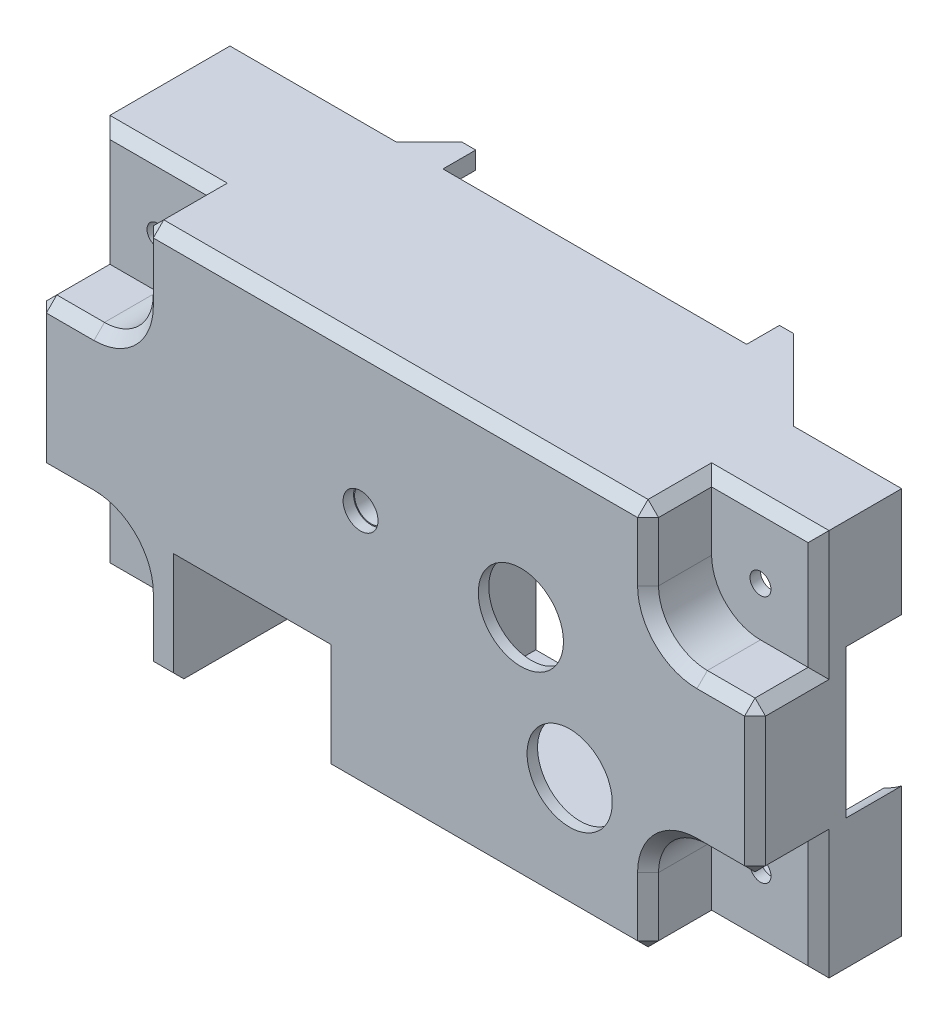
SolidWorks part; units mm, degrees
note: The reader was unsure of these and kept them because the rebuilt part matched: shared geometry of "Sketch6<3>".
ref_plane "Front Plane" through (0, 0, 0) normal (0, 0, 1) x (1, 0, 0)
ref_plane "Top Plane" through (0, 0, 0) normal (0, 1, 0) x (1, 0, 0)
ref_plane "Right Plane" through (0, 0, 0) normal (1, 0, 0) x (0, 0, -1)
sketch "Sketch1" plane through (0, 0, 0) normal (0, 0, 1) x (1, 0, 0)
  line L0 (36, -27.75) -> (29.2, -27.75) construction
  line L1 (36, -27.75) -> (51.5, -27.75) construction
  line L2 (51.5, -27.75) -> (51.5, 27.75) construction
  line L3 (51.5, 27.75) -> (36, 27.75) construction
  line L4 (-27.7, 27.75) -> (-51.5, 27.75) construction
  line L5 (-51.5, 27.75) -> (-51.5, 9.7141) construction
  line L6 (-51.5, 9.7141) -> (-51.5, 6.25) construction
  line L7 (-51.5, 6.25) -> (-51.5, -1.55) construction
  line L8 (-51.5, -1.55) -> (-51.5, -5.0141) construction
  line L9 (-51.5, -5.0141) -> (-51.5, -27.75) construction
  line L10 (-51.5, -27.75) -> (29.2, -27.75) construction
  line L11 (36, -27.75) -> (29.2, -27.75)
  line L12 (36, -27.75) -> (51.5, -27.75)
  line L13 (51.5, -27.75) -> (51.5, 27.75)
  line L14 (51.5, 27.75) -> (36, 27.75)
  line L15 (36, 27.75) -> (-51.5, 27.75)
  line L16 (-51.5, 27.75) -> (-51.5, 9.7141)
  line L17 (-51.5, 9.7141) -> (-51.5, 6.25)
  line L18 (-51.5, 6.25) -> (-51.5, -1.55)
  line L19 (-51.5, -1.55) -> (-51.5, -5.0141)
  line L20 (-51.5, -5.0141) -> (-51.5, -27.75)
  line L21 (-51.5, -27.75) -> (29.2, -27.75)
  line L22 (49, 25.25) -> (49, -25.25) construction
  line L23 (36, 25.25) -> (49, 25.25) construction
  line L24 (24.5, 25.25) -> (36, 25.25) construction
  line L25 (-23, 25.25) -> (24.5, 25.25) construction
  line L26 (-49, 25.25) -> (-27.7, 25.25) construction
  line L27 (49, -25.25) -> (36, -25.25) construction
  line L28 (36, -25.25) -> (29.2, -25.25) construction
  line L29 (29.2, -25.25) -> (-49, -25.25) construction
  line L30 (-49, -25.25) -> (-49, -5.0141) construction
  line L31 (-49, -5.0141) -> (-49, -1.55) construction
  line L32 (-49, -1.55) -> (-49, 6.25) construction
  line L33 (-49, 6.25) -> (-49, 9.7141) construction
  line L34 (-49, 9.7141) -> (-49, 25.25) construction
  line L35 (-27.7, 25.25) -> (-23, 25.25) construction
  line L36 (49, -25.25) -> (36, -25.25)
  line L37 (36, -25.25) -> (29.2, -25.25)
  line L38 (29.2, -25.25) -> (-49, -25.25)
  line L39 (-49, -25.25) -> (-49, -5.0141)
  line L40 (-49, -5.0141) -> (-49, -1.55)
  line L41 (-49, -1.55) -> (-49, 6.25)
  line L42 (-49, 6.25) -> (-49, 9.7141)
  line L43 (-49, 9.7141) -> (-49, 25.25)
  line L44 (49, 25.25) -> (49, -25.25)
  line L45 (36, 25.25) -> (49, 25.25)
  line L46 (24.5, 25.25) -> (36, 25.25)
  line L47 (-23, 25.25) -> (24.5, 25.25)
  line L48 (-27.7, 25.25) -> (-23, 25.25)
  line L49 (-49, 25.25) -> (-27.7, 25.25)
  line L50 (43.18, -9.28) -> (57.4441, -9.28)
  line L51 (34.68, -17.78) -> (34.68, -32.8438)
  line L52 (51.5, 0) -> (-51.5, 0) construction
  line L53 (0, 0) -> (0, -33.7504) construction
  line L54 (43.18, 9.28) -> (57.4441, 9.28)
  line L55 (34.68, 17.78) -> (34.68, 32.8438)
  line L56 (-34.68, -17.78) -> (-34.68, -32.8438)
  line L57 (-43.18, -9.28) -> (-57.4441, -9.28)
  line L58 (-34.68, 17.78) -> (-34.68, 32.8438)
  line L59 (-43.18, 9.28) -> (-57.4441, 9.28)
  line L64 (-10, -21.75) -> (-10, -12.25)
  line L65 (-10, -12.25) -> (-31, -12.25)
  line L66 (-31, -12.25) -> (-31, -21.75)
  line L67 (-31, -21.75) -> (-10, -21.75)
  line L68 (-10, -21.75) -> (-10, -12.25)
  line L69 (-10, -12.25) -> (-31, -12.25)
  line L70 (-31, -12.25) -> (-31, -21.75)
  line L71 (-31, -21.75) -> (-10, -21.75)
  line L72 (-5.5, 16.75) -> (-5.5, 23.25)
  line L73 (-5.5, 23.25) -> (-22, 23.25)
  line L74 (-22, 23.25) -> (-22, 16.75)
  line L75 (-22, 16.75) -> (-5.5, 16.75)
  line L76 (-5.5, 16.75) -> (-5.5, 23.25) construction
  line L77 (-5.5, 23.25) -> (-22, 23.25) construction
  line L78 (-22, 23.25) -> (-22, 16.75) construction
  line L79 (-22, 16.75) -> (-5.5, 16.75) construction
  line L80 (25, 16.75) -> (25, 23.25)
  line L81 (25, 23.25) -> (-1.8, 23.25)
  line L82 (-1.8, 23.25) -> (-1.8, 16.75)
  line L83 (-1.8, 16.75) -> (25, 16.75)
  line L84 (25, 16.75) -> (25, 23.25) construction
  line L85 (25, 23.25) -> (-1.8, 23.25) construction
  line L86 (-1.8, 23.25) -> (-1.8, 16.75) construction
  line L87 (-1.8, 16.75) -> (25, 16.75) construction
  circle A0 centre (43.5, 1.5) radius 5
  circle A1 centre (43.18, 17.78) radius 8.5
  circle A2 centre (-5, 7.25) radius 2.5
  circle A3 centre (-5, 7.25) radius 2.5
  circle A4 centre (-43.18, -17.78) radius 8.5
  circle A5 centre (17.9619, 5.5181) radius 6.1
  circle A6 centre (17.9619, 5.5181) radius 6.1
  circle A7 centre (-43.18, 17.78) radius 8.5
  circle A8 centre (24.9509, -10.9256) radius 6.1
  circle A9 centre (24.9509, -10.9256) radius 6.1
  circle A11 centre (43.18, -17.78) radius 8.5
  circle A12 centre (43.18, -17.78) radius 8.5
  dimension "D5" = 10
  dimension "D6" = 0
  dimension "D1" = 0.1
  dimension "D2" = 0.2
  dimension "D3" = 0.2
  dimension "D4" = 7
  dimension "D7" = 0
  dimension "D8" = 0
extrude "Boss-Extrude1" add sketch "Sketch1" against normal blind 1.5 contours L49 L43 L42 L41 L40 L39 L38 L37 L36 L44 L45 L46 L47 L48 | L20 L21 L11 L12 L13 L14 L15 L16 L17 L18 L19 L43 L49 L48 L47 L46 L45 L44 L36 L37 L38 L39 L40 L41 L42 | L38 L56 L21 L11 L51 L37 | L54 L44 L50 L13 | L58 L49 L48 L47 L46 L55 L15
sketch "Sketch2" plane through (0, 0, 0) normal (0, 0, 1) x (1, 0, 0)
  line L0 (34.68, 17.78) -> (34.68, 27.75) construction
  line L1 (43.18, 9.28) -> (51.5, 9.28) construction
  line L2 (43.18, -9.28) -> (51.5, -9.28) construction
  line L3 (34.68, -17.78) -> (34.68, -27.75) construction
  line L4 (-34.68, -17.78) -> (-34.68, -27.75) construction
  line L5 (-43.18, -9.28) -> (-51.5, -9.28) construction
  line L6 (-34.68, 17.78) -> (-34.68, 27.75) construction
  line L7 (-43.18, 9.28) -> (-51.5, 9.28) construction
  line L8 (34.68, 17.78) -> (34.68, 27.75)
  line L9 (43.18, 9.28) -> (51.5, 9.28)
  line L10 (43.18, -9.28) -> (51.5, -9.28)
  line L11 (34.68, -17.78) -> (34.68, -27.75)
  line L12 (-34.68, -17.78) -> (-34.68, -27.75)
  line L13 (-43.18, -9.28) -> (-51.5, -9.28)
  line L14 (-34.68, 17.78) -> (-34.68, 27.75)
  line L15 (-43.18, 9.28) -> (-51.5, 9.28)
  line L16 (-43.18, -10.78) -> (-51.5, -10.78)
  line L17 (-36.18, -17.78) -> (-36.18, -27.75)
  line L18 (-36.18, 17.78) -> (-36.18, 27.75)
  line L19 (-43.18, 10.78) -> (-51.5, 10.78)
  line L20 (43.18, 10.78) -> (51.5, 10.78)
  line L21 (36.18, 17.78) -> (36.18, 27.75)
  line L22 (36.18, -17.78) -> (36.18, -27.75)
  line L23 (43.18, -10.78) -> (51.5, -10.78)
  line L24 (-51.5, 10.78) -> (-51.5, 9.28)
  line L25 (-51.5, -9.28) -> (-51.5, -10.78)
  line L26 (-36.18, -27.75) -> (-34.68, -27.75)
  line L27 (34.68, -27.75) -> (36.18, -27.75)
  line L28 (51.5, -10.78) -> (51.5, -9.28)
  line L29 (51.5, 9.28) -> (51.5, 10.78)
  line L30 (34.68, 27.75) -> (36.18, 27.75)
  line L31 (-34.68, 27.75) -> (-36.18, 27.75)
  arc A0 (34.68, 17.78) -> (43.18, 9.28) centre (43.18, 17.78) ccw construction
  arc A1 (43.18, -9.28) -> (34.68, -17.78) centre (43.18, -17.78) ccw construction
  arc A2 (-34.68, -17.78) -> (-43.18, -9.28) centre (-43.18, -17.78) ccw construction
  arc A3 (-43.18, 9.28) -> (-34.68, 17.78) centre (-43.18, 17.78) ccw construction
  arc A4 (34.68, 17.78) -> (43.18, 9.28) centre (43.18, 17.78) ccw
  arc A5 (43.18, -9.28) -> (34.68, -17.78) centre (43.18, -17.78) ccw
  arc A6 (-34.68, -17.78) -> (-43.18, -9.28) centre (-43.18, -17.78) ccw
  arc A7 (-43.18, 9.28) -> (-34.68, 17.78) centre (-43.18, 17.78) ccw
  arc A8 (-36.18, -17.78) -> (-43.18, -10.78) centre (-43.18, -17.78) ccw
  arc A9 (-43.18, 10.78) -> (-36.18, 17.78) centre (-43.18, 17.78) ccw
  arc A10 (36.18, 17.78) -> (43.18, 10.78) centre (43.18, 17.78) ccw
  arc A11 (43.18, -10.78) -> (36.18, -17.78) centre (43.18, -17.78) ccw
  dimension "D1" = 1.5
  dimension "D2" = 1.5
  dimension "D3" = 1.5
  dimension "D4" = 1.5
extrude "Boss-Extrude2" add sketch "Sketch2" against normal up to surface (9.1 mm away)
sketch "Sketch3" plane through (0, 0, -9.1) normal (0, 0, -1) x (-1, 0, 0)
  line L0 (23.4, 27.75) -> (51.5, 27.75) construction
  line L1 (-51.5, 27.75) -> (-24.9, 27.75) construction
  line L2 (-51.5, 27.75) -> (-51.5, -27.75) construction
  line L3 (51.5, -27.75) -> (51.5, 27.75) construction
  line L4 (-51.5, -27.75) -> (51.5, -27.75) construction
  line L5 (23.4, 27.75) -> (51.5, 27.75)
  line L6 (-51.5, 27.75) -> (-24.9, 27.75)
  line L7 (-51.5, 27.75) -> (-51.5, -27.75)
  line L8 (51.5, -27.75) -> (51.5, 27.75)
  line L9 (-51.5, -27.75) -> (51.5, -27.75)
  line L10 (-34.68, 17.78) -> (-34.68, 27.75) construction
  line L11 (-51.5, 9.28) -> (-43.18, 9.28) construction
  line L12 (-43.18, -9.28) -> (-51.5, -9.28) construction
  line L13 (-34.68, -27.75) -> (-34.68, -17.78) construction
  line L14 (34.68, -17.78) -> (34.68, -27.75) construction
  line L15 (51.5, -9.28) -> (43.18, -9.28) construction
  line L16 (34.68, 27.75) -> (34.68, 17.78) construction
  line L17 (43.18, 9.28) -> (51.5, 9.28) construction
  line L18 (-34.68, 17.78) -> (-34.68, 27.75)
  line L19 (-51.5, 9.28) -> (-43.18, 9.28)
  line L20 (-43.18, -9.28) -> (-51.5, -9.28)
  line L21 (-34.68, -27.75) -> (-34.68, -17.78)
  line L22 (34.68, -17.78) -> (34.68, -27.75)
  line L23 (51.5, -9.28) -> (43.18, -9.28)
  line L24 (34.68, 27.75) -> (34.68, 17.78)
  line L25 (43.18, 9.28) -> (51.5, 9.28)
  arc A0 (-43.18, 9.28) -> (-34.68, 17.78) centre (-43.18, 17.78) ccw construction
  arc A1 (-34.68, -17.78) -> (-43.18, -9.28) centre (-43.18, -17.78) ccw construction
  arc A2 (43.18, -9.28) -> (34.68, -17.78) centre (43.18, -17.78) ccw construction
  arc A3 (34.68, 17.78) -> (43.18, 9.28) centre (43.18, 17.78) ccw construction
  arc A4 (-43.18, 9.28) -> (-34.68, 17.78) centre (-43.18, 17.78) ccw
  arc A5 (-34.68, -17.78) -> (-43.18, -9.28) centre (-43.18, -17.78) ccw
  arc A6 (43.18, -9.28) -> (34.68, -17.78) centre (43.18, -17.78) ccw
  arc A7 (34.68, 17.78) -> (43.18, 9.28) centre (43.18, 17.78) ccw
  circle A8 centre (-43.18, 17.78) radius 1.5 construction
  circle A9 centre (-43.18, -17.78) radius 1.5 construction
  circle A10 centre (43.18, -17.78) radius 1.5 construction
  circle A11 centre (43.18, 17.78) radius 1.5 construction
  circle A12 centre (-43.18, 17.78) radius 1.5
  circle A13 centre (-43.18, -17.78) radius 1.5
  circle A14 centre (43.18, -17.78) radius 1.5
  circle A15 centre (43.18, 17.78) radius 1.5
  arc M1 (36.18, -17.78) -> (43.18, -10.78) centre (43.18, -17.78) cw
  line M2 (43.18, -10.78) -> (51.5, -10.78)
  line M3 (51.5, -10.78) -> (51.5, -9.28)
  line M4 (51.5, -9.28) -> (43.18, -9.28)
  arc M5 (43.18, -9.28) -> (34.68, -17.78) centre (43.18, -17.78) ccw
  line M6 (34.68, -17.78) -> (34.68, -27.75)
  line M7 (34.68, -27.75) -> (36.18, -27.75)
  line M8 (36.18, -27.75) -> (36.18, -17.78)
extrude "Boss-Extrude3" add sketch "Sketch3" along normal blind 1.5 contours M8 M1 M2 M3 M4 M5 M6 M7 | L9 L8 A14 M8 M2 M1 | L21 A5 L20 L7 L9 A13 | L19 A4 L18 L6 L7 A12 | L24 A7 L25 L8 L5 A15
sketch "Sketch4" plane through (0, 0, 0) normal (0, 0, 1) x (1, 0, 0)
  circle A0 centre (43.5, 1.5) radius 6.5
  dimension "D1" = 13
extrude "Boss-Extrude4" add sketch "Sketch4" against normal up to surface (4 mm away)
sketch "Sketch5" plane through (0, 0, -4) normal (0, 0, -1) x (-1, 0, 0)
  circle A0 centre (-43.5, 1.5) radius 6.5 construction
  circle A1 centre (-43.5, 1.5) radius 6.5
  circle A2 centre (-43.5, 1.5) radius 5.1
  dimension "D1" = 10.2
extrude "Boss-Extrude5" add sketch "Sketch5" along normal blind 4
sketch "Sketch6" plane through (0, 0, -10.6) normal (0, 0, -1) x (-1, 0, 0)
  line L0 (51.5, -27.75) -> (51.5, 27.75) construction
  line L1 (51.5, -27.75) -> (51.5, 27.75)
  line L2 (-51.5, -27.75) -> (51.5, -27.75) construction
  line L3 (-51.5, -27.75) -> (51.5, -27.75)
  line L4 (-51.5, 27.75) -> (-51.5, -27.75) construction
  line L5 (-51.5, 27.75) -> (-51.5, -27.75)
  line L6 (49, -25.25) -> (-49, -25.25) construction
  line L7 (49, -25.25) -> (-49, -25.25)
  line L8 (-49, -25.25) -> (-49, 25.25) construction
  line L9 (-49, -25.25) -> (-49, 25.25)
  line L10 (49, 25.25) -> (49, -25.25) construction
  line L11 (49, 25.25) -> (49, -25.25)
  line L12 (-49, 25.25) -> (49, 25.25) construction
  line L13 (-49, 25.25) -> (49, 25.25)
  line L14 (34.68, 27.75) -> (51.5, 27.75) construction
  line L15 (-34.68, 27.75) -> (51.5, 27.75)
  line L16 (-51.5, 27.75) -> (-34.68, 27.75) construction
  line L17 (-51.5, 27.75) -> (-34.68, 27.75)
  line L18 (51.5, -9.28) -> (43.18, -9.28) construction
  line L19 (51.5, -9.28) -> (43.18, -9.28)
  line L20 (43.18, 9.28) -> (51.5, 9.28) construction
  line L21 (43.18, 9.28) -> (51.5, 9.28)
  line L22 (34.68, -17.78) -> (34.68, -27.75) construction
  line L23 (34.68, -17.78) -> (34.68, -27.75)
  line L24 (-34.68, -27.75) -> (-34.68, -17.78) construction
  line L25 (-34.68, -27.75) -> (-34.68, -17.78)
  line L26 (34.68, 27.75) -> (34.68, 17.78) construction
  line L27 (34.68, 27.75) -> (34.68, 17.78)
  line L28 (-34.68, 17.78) -> (-34.68, 27.75) construction
  line L29 (-34.68, 17.78) -> (-34.68, 27.75)
  line L30 (-51.5, 9.28) -> (-43.18, 9.28) construction
  line L31 (-51.5, 9.28) -> (-43.18, 9.28)
  line L32 (-43.18, -9.28) -> (-51.5, -9.28) construction
  line L33 (-43.18, -9.28) -> (-51.5, -9.28)
  point P9 (-35.2082, 27.75)
  line M10 (34.68, -27.75) -> (51.5, -27.75)
  line M11 (51.5, -27.75) -> (51.5, -9.28)
  line M12 (51.5, -9.28) -> (43.18, -9.28)
  line M14 (34.68, -17.78) -> (34.68, -27.75)
extrude "Boss-Extrude6" add sketch "Sketch6" against normal up to surface (9.1 mm away) contours L21 L11 L1 M12 | L29 L13 L27 L15 | L25 L3 L7 M14 | L33 L9 L31 L5 up to face at (50, 1.5, -1.5)
extrude "Boss-Extrude7" add sketch "Sketch6<3>" along normal up to surface (17.2 mm away) contours L11 L7 M12 M14 M10 M11 | L25 L3 L7 M14 | L21 L11 L1 M12 | L15 L27 L13 L11 L21 L1 | L29 L13 L27 L15 | L5 L31 L9 L13 L29 L17 | L33 L9 L31 L5 | L9 L33 L5 L3 L25 L7
sketch "Sketch6<3>" plane through (0, 0, -10.6) normal (0, 0, -1) x (-1, 0, 0) same geometry as "Sketch6"
sketch "Sketch7" plane through (0, -27.75, 0) normal (0, -1, 0) x (1, 0, 0)
  line L0 (24.5, -32.5) -> (36, -21) construction
  line L1 (24.5, -32.5) -> (36, -21)
  line L2 (36, -21) -> (60.9783, -21)
  line L3 (60.9783, -21) -> (60.9783, -33.2179)
  line L4 (60.9783, -33.2179) -> (24.5, -32.5)
extrude "Cut-Extrude1" cut sketch "Sketch7" against normal through all
sketch "Sketch8" plane through (0, 0, -21) normal (0, 0, -1) x (-1, 0, 0)
  circle A2 centre (-43.5, 1.5) radius 13.3
  circle A3 centre (-43.5, 1.5) radius 13.3
  dimension "D1" = 0.8
extrude "Cut-Extrude2" cut sketch "Sketch8" against normal offset from surface (8 mm away) 0.5
sketch "Sketch9" plane through (0, 27.75, 0) normal (0, 1, 0) x (1, 0, 0)
  line L0 (24.5, 32.5) -> (36, 21) construction
  line L1 (24.5, 32.5) -> (36, 21)
  line L2 (-27.7, 27.8) -> (-23, 32.5) construction
  line L3 (-27.7, 27.8) -> (-23, 32.5)
  line L4 (-23, 32.5) -> (-21, 32.5)
  line L5 (24.5, 32.5) -> (-23, 32.5) construction
  line L6 (-21, 32.5) -> (-21, 25.7612)
  line L7 (-21, 25.7612) -> (-27.7, 25.7612)
  line L8 (-27.7, 25.7612) -> (-27.7, 27.8)
  line L9 (24.5, 32.5) -> (22.5, 32.5)
  line L10 (22.5, 32.5) -> (22.5, 25.7612)
  line L11 (22.5, 25.7612) -> (31.2388, 25.7612)
  line L12 (24.5, 32.5) -> (22.5, 32.5)
  line M3 (29.2, 27.8) -> (-51.5, 27.8)
  dimension "D1" = 2
  dimension "D2" = 2
extrude "Boss-Extrude8" add sketch "Sketch9" against normal up to surface (2.5 mm away) contours L6 L4 L3 M3 | L9 L10 L1 M3 up to face at (6.52, 25.25, -14.3)
sketch "Sketch11" plane through (-51.5, 0, 0) normal (-1, 0, 0) x (0, 0, 1)
  line L0 (-29.8, 6.25) -> (-29.8, -1.55) construction
  line L1 (-29.8, 6.25) -> (-29.8, -1.55)
  line L2 (-21.8, 6.25) -> (-21.8, -1.55)
  arc A0 (-27.8, 9.7141) -> (-29.8, 6.25) centre (-25.8, 6.25) ccw construction
  arc A1 (-26.1783, 2.2679) -> (-29.8, 6.25) centre (-25.8, 6.25) ccw
  arc A2 (-29.8, -1.55) -> (-27.8, -5.0141) centre (-25.8, -1.55) ccw construction
  arc A3 (-29.8, -1.55) -> (-27.2267, 2.1869) centre (-25.8, -1.55) ccw
extrude "Cut-Extrude3" cut sketch "Sketch11" against normal blind 10.5
sketch "Sketch12" plane through (0, 0, 0) normal (0, 0, 1) x (1, 0, 0)
  line L6 (-31.8, -22.55) -> (-9.2, -22.55)
  line L7 (-31.8, -22.55) -> (-31.8, -34.2648)
  line L8 (-31.8, -34.2648) -> (-9.2, -34.2648)
  line L9 (-31.8, -22.55) -> (-9.2, -22.55)
  line L10 (-31.8, -11.45) -> (-31.8, -22.55)
  line L11 (-9.2, -11.45) -> (-31.8, -11.45)
  line L12 (-9.2, -22.55) -> (-9.2, -11.45)
  line L13 (-31.8, -22.55) -> (-9.2, -22.55)
  line L14 (-31.8, -11.45) -> (-31.8, -22.55)
  line L15 (-9.2, -11.45) -> (-31.8, -11.45)
  line L16 (-9.2, -22.55) -> (-9.2, -11.45)
  line L17 (-9.2, -22.55) -> (-9.2, -34.2648)
  point P3 (-8.9745, -22.25)
  line M17 (-36.18, -27.75) -> (36.18, -27.75)
  line M28 (-10, -21.75) -> (-31, -21.75)
  line M29 (-31, -21.75) -> (-31, -12.25)
  line M30 (-31, -12.25) -> (-10, -12.25)
  line M31 (-10, -12.25) -> (-10, -21.75)
  dimension "D1" = 0.8
extrude "Cut-Extrude4" cut sketch "Sketch12" against normal through all contours L17 L6 L7 M17 | L6 L16 L15 L14 M31 M28 M29 M30 | M28 M31 M30 M29
sketch "Sketch13" plane through (0, 0, -27.8) normal (0, 0, -1) x (-1, 0, 0)
  line L1 (31.8, -27.75) -> (9.2, -27.75)
  line L2 (31.8, -27.75) -> (31.8, -25.25)
  line L3 (31.8, -25.25) -> (9.2, -25.25)
  line L4 (9.2, -27.75) -> (9.2, -25.25)
extrude "Boss-Extrude9" add sketch "Sketch13" against normal up to surface (4.8 mm away)
sketch "Sketch14" plane through (0, 0, -1.5) normal (0, 0, -1) x (-1, 0, 0)
  line L0 (9.2, -11.45) -> (31.8, -11.45) construction
  line L1 (31.8, -11.45) -> (31.8, -25.25) construction
  line L2 (9.2, -11.45) -> (9.2, -25.25) construction
  line L3 (9.2, -11.45) -> (31.8, -11.45)
  line L4 (31.8, -11.45) -> (31.8, -25.25)
  line L5 (9.2, -11.45) -> (9.2, -25.25)
  line L6 (7.7, -9.95) -> (7.7, -25.25)
  line L7 (7.7, -9.95) -> (33.3, -9.95)
  line L8 (33.3, -9.95) -> (33.3, -25.25)
  line L9 (33.3, -25.25) -> (31.8, -25.25)
  line L10 (9.2, -25.25) -> (7.7, -25.25)
  dimension "D1" = 1.5
extrude "Boss-Extrude10" add sketch "Sketch14" along normal up to surface (26.3 mm away) up to face at (-23.7667, -19.338, -27.8)
sketch "Sketch15" plane through (0, 0, -23) normal (0, 0, 1) x (1, 0, 0)
  line L1 (-31.8, -11.45) -> (-31.8, -27.75) construction
  line L2 (-31, -22.55) -> (-10, -22.55)
  line L3 (-34.7993, -22.55) -> (-5.935, -22.55)
  line L4 (-31.8, -11.45) -> (-31.8, -27.75)
  line L5 (-9.2, -11.45) -> (-9.2, -27.75) construction
  line L6 (-9.2, -11.45) -> (-9.2, -27.75)
  line L7 (-31.8, -25.25) -> (-9.2, -25.25) construction
  line L8 (-31.8, -25.25) -> (-9.2, -25.25)
  point P6 (-34.7993, -22.55)
  point P8 (-5.935, -22.55)
  line M5 (-9.2, -25.25) -> (-31.8, -25.25)
  dimension "D1" = 0.8
extrude "Boss-Extrude11" add sketch "Sketch15" against normal blind 2 contours L6 L3 L4 M5
sketch "Sketch16" plane through (0, 0, -1.5) normal (0, 0, -1) x (-1, 0, 0)
  circle A1 centre (5, 7.25) radius 3.35
  circle A2 centre (5, 7.25) radius 2.35
  circle A3 centre (5, 7.25) radius 2.35
  dimension "D1" = 0.2
  dimension "D2" = 1
extrude "Boss-Extrude12" add sketch "Sketch16" along normal blind 20
fillet "Fillet1" radius 8 1 edges at (-1.65, 7.25, -1.5)
chamfer "Chamfer1" distance 2 angle 45 19 edges at (-33.99, -25.25, -1.5) (-46.09, -9.28, -1.5) (-37.1696, -11.7696, -1.5) (-49, 0, -1.5) (-46.09, 9.28, -1.5) (-34.68, 21.515, -1.5) (-37.1696, 11.7696, -1.5) (0, 25.25, -1.5) (49, 7.1221, -1.5) (49, -5.6221, -1.5) (46.09, 9.28, -1.5) (34.68, 21.515, -1.5) (37.1696, 11.7696, -1.5) (46.09, -9.28, -1.5) (34.68, -21.515, -1.5) (37.1696, -11.7696, -1.5) (-20.5, -9.95, -1.5) (-7.7, -17.6, -1.5) (13.49, -25.25, -1.5)
chamfer "Chamfer2" distance 1.5 angle 45 33 edges at (-47.34, -10.78, 0) (-36.18, -22.765, 0) (-38.2303, -12.8303, 0) (-36.18, 22.765, 0) (-47.34, 10.78, 0) (-38.2303, 12.8303, 0) (47.34, 10.78, 0) (36.18, 22.765, 0) (38.2303, 12.8303, 0) (36.18, -22.765, 0) (47.34, -10.78, 0) (38.2303, -12.8303, 0) (-33.99, -27.75, 0) (-36.18, -27.75, -4.55) (-43.84, -27.75, -9.1) (-51.5, -19.265, -9.1) (-51.5, -10.78, -4.55) (-51.5, 0, 0) (-51.5, 10.78, -4.55) (-51.5, 19.265, -9.1) (-43.84, 27.75, -9.1) (-36.18, 27.75, -4.55) (0, 27.75, 0) (36.18, 27.75, -4.55) (43.84, 27.75, -9.1) (51.5, 19.265, -9.1) (51.5, 10.78, -4.55) (51.5, 0, 0) (51.5, -10.78, -4.55) (51.5, -19.265, -9.1) (43.84, -27.75, -9.1) (36.18, -27.75, -4.55) (13.49, -27.75, 0)
